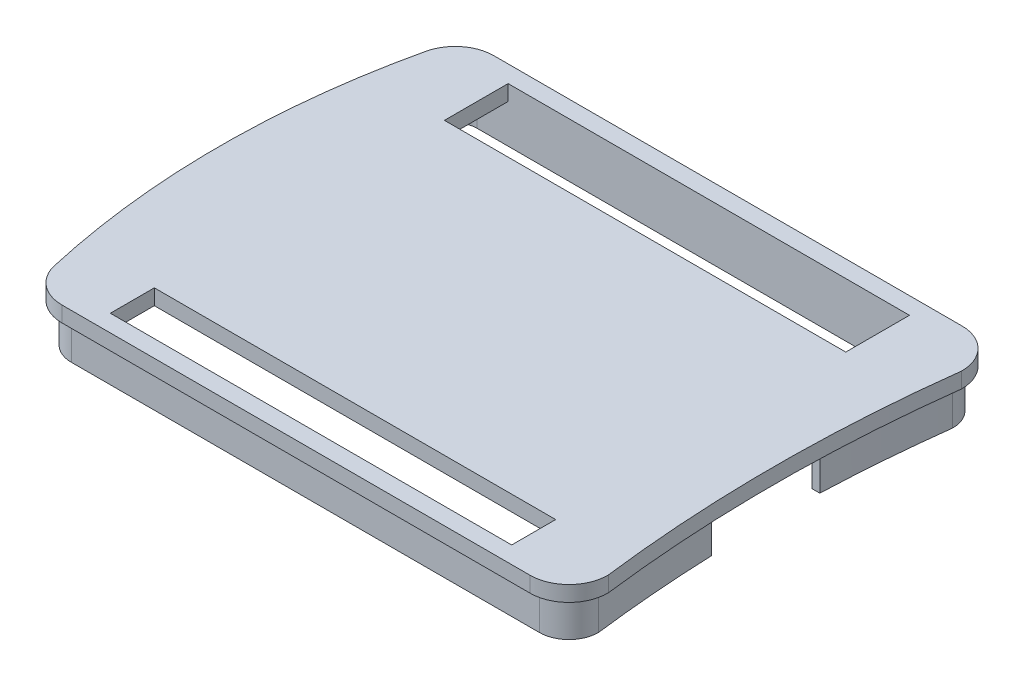
SolidWorks part; units mm, degrees
ref_plane "Front Plane" through (0, 0, 0) normal (0, 0, 1) x (1, 0, 0)
ref_plane "Top Plane" through (0, 0, 0) normal (0, 1, 0) x (1, 0, 0)
ref_plane "Right Plane" through (0, 0, 0) normal (1, 0, 0) x (0, 0, -1)
sketch "Sketch1" plane through (0, 0, 0) normal (0, 1, 0) x (1, 0, 0)
  line L0 (0, 20.2635) -> (0, -20.6983) construction
  line L1 (-48.5386, 0) -> (50.9036, 0) construction
  line L2 (-36.322, 3.1321) -> (-36.322, 0) construction
  line L3 (30.48, 26.67) -> (-38.692, 26.67) construction
  line L4 (32.868, 0.8812) -> (32.868, 0) construction
  line L5 (30.48, 26.67) -> (-29.9413, 26.67)
  line L6 (30.48, -26.67) -> (-29.9413, -26.67)
  circle A0 centre (30.48, 22.86) radius 1.6
  circle A1 centre (30.48, 22.86) radius 3.81 construction
  circle A2 centre (-30.48, 20.32) radius 1.6
  circle A3 centre (-30.48, 20.32) radius 3.81 construction
  arc A4 (34.29, -22.86) -> (34.29, 22.86) centre (217.3271, 0) cw
  arc A5 (-33.6457, -23.7168) -> (-33.6457, 23.7168) centre (70.104, 0) cw
  arc A6 (-33.6457, 23.7168) -> (-29.9413, 26.67) centre (-29.9413, 22.87) cw
  arc A7 (30.48, 26.67) -> (34.29, 22.86) centre (30.48, 22.86) cw
  circle A8 centre (30.48, -22.86) radius 1.6
  arc A9 (30.48, -26.67) -> (34.29, -22.86) centre (30.48, -22.86) ccw
  circle A10 centre (30.48, -22.86) radius 3.81 construction
  circle A11 centre (-30.48, -20.32) radius 3.81 construction
  circle A12 centre (-30.48, -20.32) radius 1.6
  arc A13 (-33.6457, -23.7168) -> (-29.9413, -26.67) centre (-29.9413, -22.87) ccw
  point P21 (-32.9261, 26.67)
  dimension "D1" = 3.2
  dimension "D4" = 7.62
  dimension "D6" = 3.2
  dimension "D8" = 7.62
  dimension "D11" = 3.8
  dimension "D2" = 22.86
  dimension "D3" = 30.48
  dimension "D5" = 30.48
  dimension "D7" = 40.64
  dimension "D9" = 2.388
  dimension "D10" = 70.612
sketch "Sketch2" plane through (0, 0, 0) normal (0, 1, 0) x (1, 0, 0)
  line L14 (-29.9413, -27.87) -> (30.48, -27.87)
  line L15 (30.48, 27.87) -> (-29.9413, 27.87)
  line L16 (-29.9413, -27.87) -> (30.48, -27.87)
  line L17 (30.48, 27.87) -> (-29.9413, 27.87)
  arc A30 (35.4894, 22.7802) -> (30.48, 27.87) centre (30.48, 22.86) ccw
  arc A31 (35.4894, 22.7802) -> (35.4894, -22.7802) centre (217.3271, 0) ccw
  arc A32 (30.48, -27.87) -> (35.4894, -22.7802) centre (30.48, -22.86) ccw
  arc A33 (-34.8156, -23.9842) -> (-29.9413, -27.87) centre (-29.9413, -22.87) ccw
  arc A34 (-34.8156, 23.9842) -> (-34.8156, -23.9842) centre (70.104, 0) ccw
  arc A35 (-29.9413, 27.87) -> (-34.8156, 23.9842) centre (-29.9413, 22.87) ccw
  arc A36 (35.4894, 22.7802) -> (30.48, 27.87) centre (30.48, 22.86) ccw
  arc A37 (35.4894, 22.7802) -> (35.4894, -22.7802) centre (217.3271, 0) ccw
  arc A38 (30.48, -27.87) -> (35.4894, -22.7802) centre (30.48, -22.86) ccw
  arc A39 (-34.8156, -23.9842) -> (-29.9413, -27.87) centre (-29.9413, -22.87) ccw
  arc A40 (-34.8156, 23.9842) -> (-34.8156, -23.9842) centre (70.104, 0) ccw
  arc A41 (-29.9413, 27.87) -> (-34.8156, 23.9842) centre (-29.9413, 22.87) ccw
  dimension "D1" = 1.2
extrude "Boss-Extrude1" add sketch "Sketch2" along normal blind 2
sketch "Sketch3" plane through (0, 0, 0) normal (0, -1, 0) x (1, 0, 0)
  line L14 (30.48, 25.67) -> (-29.9413, 25.67)
  line L15 (-29.9413, -25.67) -> (30.48, -25.67)
  line L18 (-29.9413, -26.67) -> (30.48, -26.67)
  line L19 (30.48, 26.67) -> (-29.9413, 26.67)
  line L20 (-29.9413, -26.67) -> (30.48, -26.67)
  line L21 (30.48, 26.67) -> (-29.9413, 26.67)
  arc A30 (33.2894, 22.9174) -> (30.48, 25.67) centre (30.48, 22.86) ccw
  arc A31 (-29.9413, 25.67) -> (-32.6709, 23.494) centre (-29.9413, 22.87) ccw
  arc A32 (-32.6709, 23.494) -> (-32.6709, -23.494) centre (70.104, 0) ccw
  arc A33 (-32.6709, -23.494) -> (-29.9413, -25.67) centre (-29.9413, -22.87) ccw
  arc A34 (30.48, -25.67) -> (33.2894, -22.9174) centre (30.48, -22.86) ccw
  arc A35 (33.2894, 22.9174) -> (33.2894, -22.9174) centre (217.3271, 0) ccw
  arc A42 (34.29, 22.86) -> (30.48, 26.67) centre (30.48, 22.86) ccw
  arc A43 (34.29, 22.86) -> (34.29, -22.86) centre (217.3271, 0) ccw
  arc A44 (30.48, -26.67) -> (34.29, -22.86) centre (30.48, -22.86) ccw
  arc A45 (-33.6457, -23.7168) -> (-29.9413, -26.67) centre (-29.9413, -22.87) ccw
  arc A46 (-33.6457, 23.7168) -> (-33.6457, -23.7168) centre (70.104, 0) ccw
  arc A47 (-29.9413, 26.67) -> (-33.6457, 23.7168) centre (-29.9413, 22.87) ccw
  arc A48 (34.29, 22.86) -> (30.48, 26.67) centre (30.48, 22.86) ccw
  arc A49 (34.29, 22.86) -> (34.29, -22.86) centre (217.3271, 0) ccw
  arc A50 (30.48, -26.67) -> (34.29, -22.86) centre (30.48, -22.86) ccw
  arc A51 (-33.6457, -23.7168) -> (-29.9413, -26.67) centre (-29.9413, -22.87) ccw
  arc A52 (-33.6457, 23.7168) -> (-33.6457, -23.7168) centre (70.104, 0) ccw
  arc A53 (-29.9413, 26.67) -> (-33.6457, 23.7168) centre (-29.9413, 22.87) ccw
  dimension "D1" = 0
  dimension "D2" = 1
extrude "Boss-Extrude2" add sketch "Sketch3" along normal blind 5
sketch "Sketch4" plane through (0, 2, 0) normal (0, 1, 0) x (1, 0, 0)
  line L1 (-25.9006, 25.67) -> (25.8994, 25.67)
  line L2 (-25.9006, 25.67) -> (-25.9006, 17.45)
  line L3 (-25.9006, 17.45) -> (25.8994, 17.45)
  line L4 (25.8994, 25.67) -> (25.8994, 17.45)
  line L5 (-25.9006, -25.67) -> (25.8994, -25.67)
  line L6 (-25.9006, -25.67) -> (-25.9006, -19.99)
  line L7 (-25.9006, -19.99) -> (25.8994, -19.99)
  line L8 (25.8994, -25.67) -> (25.8994, -19.99)
  line L9 (-29.9413, -27.87) -> (30.48, -27.87) construction
  line L10 (30.48, 27.87) -> (-29.9413, 27.87) construction
  dimension "D1" = 51.8
  dimension "D2" = 5.68
  dimension "D3" = 2.2
  dimension "D4" = 9.59
  dimension "D5" = 2.2
  dimension "D6" = 8.22
extrude "Cut-Extrude1" cut sketch "Sketch4" against normal up to surface (2 mm away) up to face at (-0.1484, 0, 0)
sketch "Sketch6" plane through (0, 0, 0) normal (0, -1, 0) x (1, 0, 0)
  line L0 (-36.3261, 16) -> (-34.1008, 16)
  line L1 (-48.5386, 0) -> (50.9036, 0) construction
  line L2 (-36.3261, -16) -> (-34.1008, -16)
  arc A0 (-34.8156, 23.9842) -> (-34.8156, -23.9842) centre (70.104, 0) ccw construction
  arc A1 (-32.6709, 23.494) -> (-32.6709, -23.494) centre (70.104, 0) ccw construction
  arc A2 (-32.6709, 23.494) -> (-32.6709, -23.494) centre (70.104, 0) ccw construction
  arc A3 (-36.3261, 16) -> (-36.3261, -16) centre (70.104, 0) ccw
  arc A4 (-34.1008, 16) -> (-34.1008, -16) centre (70.104, 0) ccw
  dimension "D1" = 16
  dimension "D2" = 16
extrude "Boss-Extrude3" add sketch "Sketch6" along normal up to surface (5 mm away) up to face at (-0.1484, -5, 0)
sketch "Sketch8" plane through (0, -5, 0) normal (0, -1, 0) x (1, 0, 0)
  line L0 (-48.5386, 0) -> (50.9036, 0) construction
  line L1 (29.4608, -7) -> (35.4381, -7)
  line L2 (29.4608, -7) -> (29.4608, 7)
  line L3 (29.4608, 7) -> (35.4381, 7)
  line L4 (35.4381, -7) -> (35.4381, 7)
  line L5 (29.4608, -7) -> (35.4381, 7) construction
  line L6 (29.4608, 7) -> (35.4381, -7) construction
  point P0 (32.4495, 0)
  dimension "D1" = 14
extrude "Cut-Extrude3" cut sketch "Sketch8" against normal blind 4
sketch "Sketch9" plane through (0, -5, 0) normal (0, -1, 0) x (-1, 0, 0)
  line L0 (48.5386, 0) -> (-50.9036, 0) construction
  line L1 (40.2459, -16.2) -> (30.4541, -16.2)
  line L2 (40.2459, -16.2) -> (40.2459, 16.2)
  line L3 (40.2459, 16.2) -> (30.4541, 16.2)
  line L4 (30.4541, -16.2) -> (30.4541, 16.2)
  line L5 (40.2459, -16.2) -> (30.4541, 16.2) construction
  line L6 (40.2459, 16.2) -> (30.4541, -16.2) construction
  point P0 (35.35, 0)
  dimension "D1" = 32.4
extrude "Cut-Extrude4" cut sketch "Sketch9" against normal blind 4
